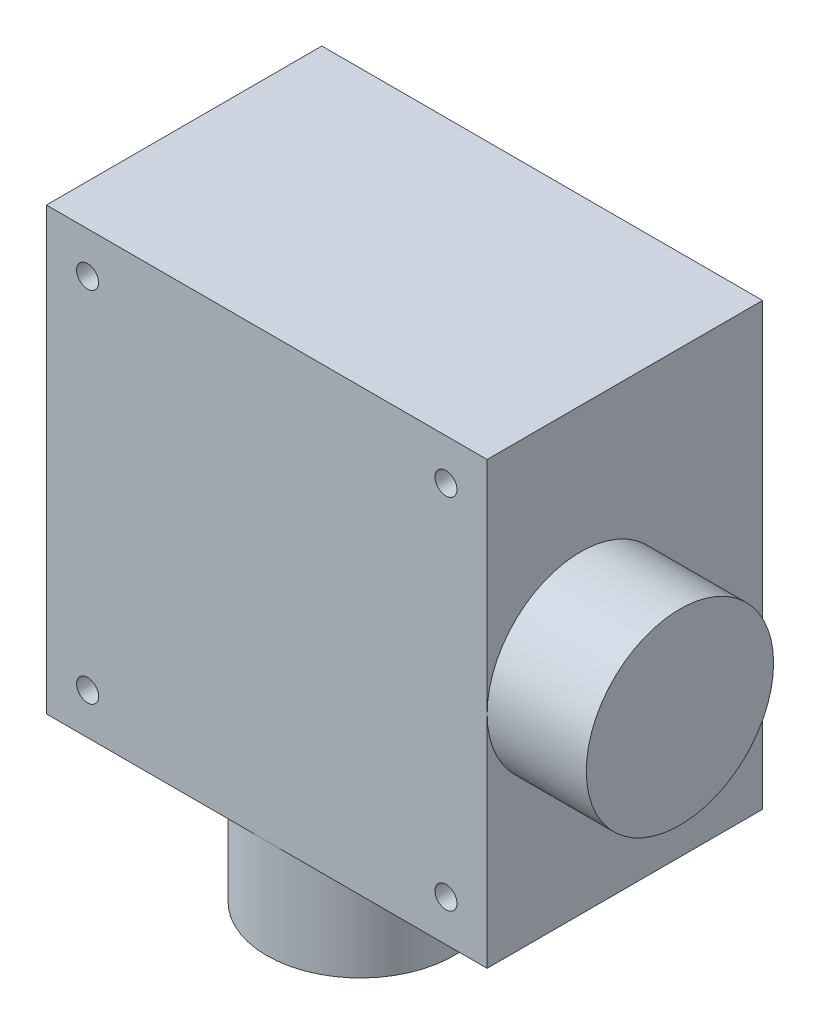
SolidWorks part; units mm, degrees
ref_plane "Спереди" through (0, 0, 0) normal (0, 0, 1) x (1, 0, 0)
ref_plane "Сверху" through (0, 0, 0) normal (0, 1, 0) x (1, 0, 0)
ref_plane "Справа" through (0, 0, 0) normal (1, 0, 0) x (0, 0, -1)
sketch "Sketch1" plane through (0, 0, 0) normal (0, 0, 1) x (1, 0, 0)
  line L0 (0, 20) -> (0, -20) construction
  line L1 (-20, 20) -> (20, 20)
  line L2 (-20, 20) -> (-20, -20)
  line L3 (-20, -20) -> (20, -20)
  line L4 (20, 20) -> (20, -20)
  line L5 (-20, 0) -> (20, 0) construction
  dimension "D1" = 40
extrude "Boss-Extrude1" add sketch "Sketch1" along normal blind 25
sketch "Sketch2" plane through (0, -20, 0) normal (0, -1, 0) x (1, 0, 0)
  line L0 (0, 0) -> (0, 25) construction
  line L1 (-20, 0) -> (20, 0) construction
  line L2 (-20, 25) -> (20, 25) construction
  circle A0 centre (0, 16.5) radius 8.5
  dimension "D1" = 17
extrude "Boss-Extrude2" add sketch "Sketch2" along normal blind 9
ref_plane "Plane1" through (0, 0, 0) normal (0.7071, 0.7071, 0) x (0.7071, -0.7071, 0)
mirror "Mirror1" about plane through (0, 0, 0) normal (0.7071, 0.7071, 0) of "Boss-Extrude2"
ref_axis "Axis1" through (0, 0, -25.5153) along (0, 0, 1)
sketch "Sketch3" plane through (0, 0, 25) normal (0, 0, 1) x (1, 0, 0)
  line L0 (-20, 20) -> (20, -20) construction
  line L1 (-20, -20) -> (20, 20) construction
  circle A0 centre (-16.2635, 16.2635) radius 1
  circle A1 centre (16.2635, 16.2635) radius 1
  circle A2 centre (-16.2635, -16.2635) radius 1
  circle A3 centre (16.2635, -16.2635) radius 1
  dimension "D1" = 2
  dimension "D2" = 46
extrude "Cut-Extrude1" cut sketch "Sketch3" against normal blind 10
